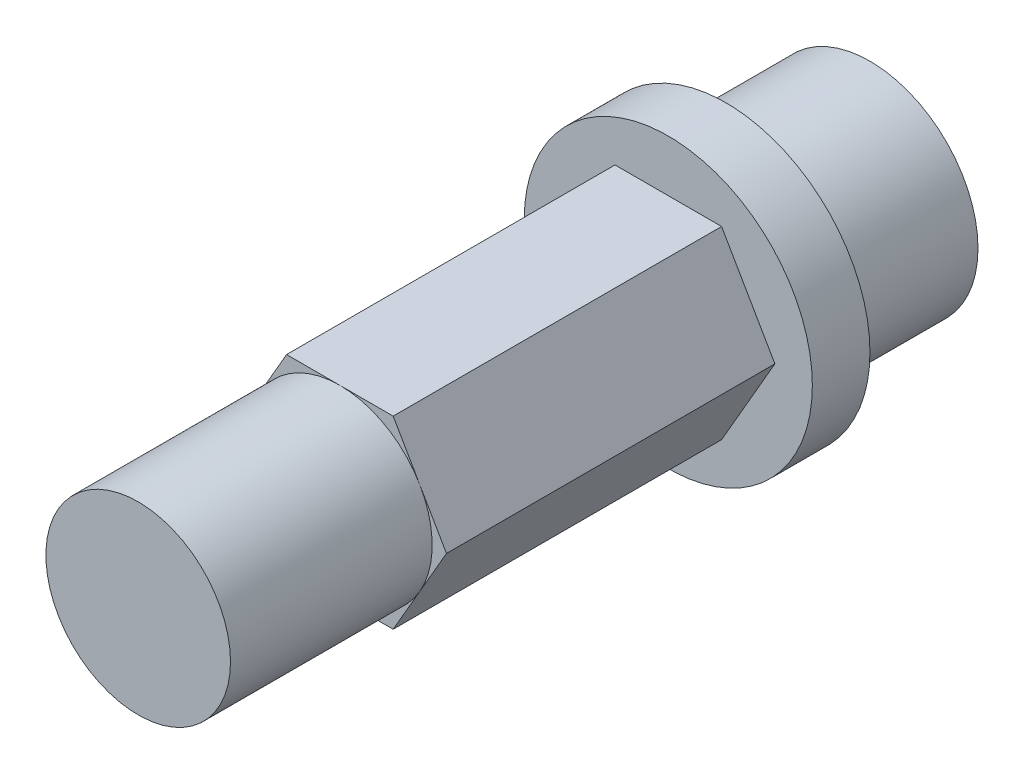
SolidWorks part; units mm, degrees
ref_plane "Front Plane" through (0, 0, 0) normal (0, 0, 1) x (1, 0, 0)
ref_plane "Top Plane" through (0, 0, 0) normal (0, 1, 0) x (1, 0, 0)
ref_plane "Right Plane" through (0, 0, 0) normal (1, 0, 0) x (0, 0, -1)
sketch "Sketch1" plane through (0, 0, 0) normal (0, 0, 1) x (1, 0, 0)
  circle A0 centre (0, 0) radius 3.75
  dimension "D1" = 7.5
extrude "Boss-Extrude1" add sketch "Sketch1" along normal blind 5
sketch "Sketch2" plane through (0, 0, 5) normal (0, 0, 1) x (1, 0, 0)
  circle A0 centre (0, 0) radius 5
  dimension "D1" = 10
extrude "Boss-Extrude2" add sketch "Sketch2" along normal blind 2
sketch "Sketch3" plane through (0, 0, 7) normal (0, 0, 1) x (1, 0, 0)
  line L7 (3.7, 0) -> (1.85, 3.2043)
  line L8 (1.85, 3.2043) -> (-1.85, 3.2043)
  line L9 (-1.85, 3.2043) -> (-3.7, 0)
  line L10 (-3.7, 0) -> (-1.85, -3.2043)
  line L11 (-1.85, -3.2043) -> (1.85, -3.2043)
  line L12 (1.85, -3.2043) -> (3.7, 0)
  circle A0 centre (0, 0) radius 3.7 construction
  circle A1 centre (0, 0) radius 3.2043 construction
  dimension "D1" = 7.4
extrude "Boss-Extrude3" add sketch "Sketch3" along normal blind 11.4
sketch "Sketch4" plane through (0, 0, 18.4) normal (0, 0, 1) x (1, 0, 0)
  line L2 (-1.85, 3.2043) -> (-3.7, 0) construction
  circle A0 centre (0, 0) radius 3.2043
extrude "Boss-Extrude4" add sketch "Sketch4" along normal blind 7
